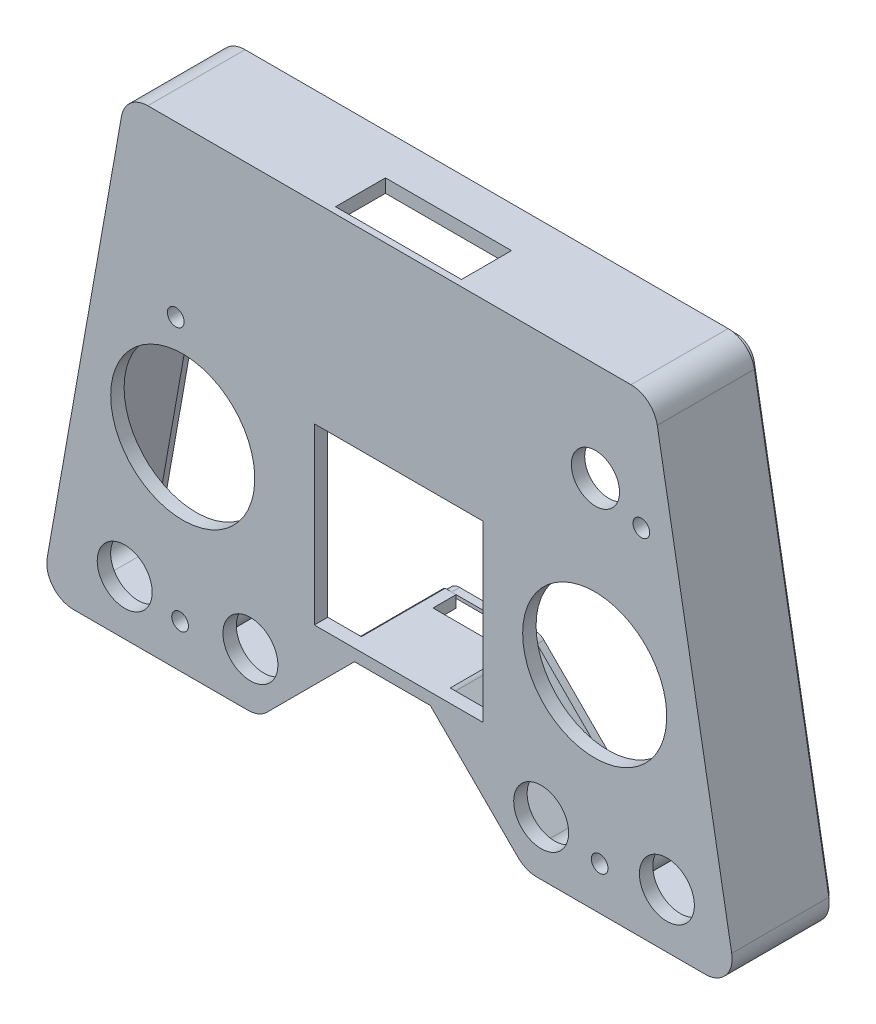
SolidWorks part; units mm, degrees
ref_plane "前视基准面" through (0, 0, 0) normal (0, 0, 1) x (1, 0, 0)
ref_plane "上视基准面" through (0, 0, 0) normal (0, 1, 0) x (1, 0, 0)
ref_plane "右视基准面" through (0, 0, 0) normal (1, 0, 0) x (0, 0, -1)
other "Configuration Table"
sketch "草图1" plane through (0, 0, 0) normal (0, 0, 1) x (1, 0, 0)
  line L0 (-11.561, 23.55) -> (-22.663, -39.125)
  line L1 (-18.737, -43.807) -> (7.32, -43.807)
  line L2 (10.139, -42.64) -> (23.192, -29.587)
  line L3 (23.201, -29.583) -> (34.512, -29.583)
  line L4 (34.521, -29.587) -> (47.574, -42.64)
  line L5 (50.393, -43.807) -> (75.552, -43.807)
  line L6 (79.479, -39.125) -> (68.376, 23.55)
  line L7 (64.45, 26.842) -> (-7.635, 26.842)
  arc A0 (-7.635, 26.842) -> (-11.561, 23.55) centre (-7.635, 22.855) ccw
  arc A1 (-22.663, -39.125) -> (-18.737, -43.807) centre (-18.737, -39.82) ccw
  arc A2 (7.32, -43.807) -> (10.139, -42.64) centre (7.3205, -39.8198) ccw
  arc A3 (23.192, -29.587) -> (23.201, -29.583) centre (23.2013, -29.5959) cw
  arc A4 (34.512, -29.583) -> (34.521, -29.587) centre (34.5117, -29.5959) cw
  arc A5 (47.574, -42.64) -> (50.393, -43.807) centre (50.3925, -39.8198) ccw
  arc A6 (75.552, -43.807) -> (79.479, -39.125) centre (75.5524, -39.8195) ccw
  arc A7 (68.376, 23.55) -> (64.45, 26.842) centre (64.45, 22.855) ccw
extrude "上壳外形_高14.5" add sketch "草图1" along normal blind 14.5
sketch "草图2" plane through (0, 0, 0) normal (0, 0, 1) x (1, 0, 0)
  line L0 (-9.591, 23.202) -> (-20.693, -39.473)
  line L1 (-18.737, -41.807) -> (7.32, -41.807)
  line L2 (8.725, -41.226) -> (21.778, -28.173)
  line L3 (23.201, -27.583) -> (34.512, -27.583)
  line L4 (35.935, -28.173) -> (48.988, -41.226)
  line L5 (50.393, -41.807) -> (75.552, -41.807)
  line L6 (77.509, -39.473) -> (66.406, 23.202)
  line L7 (64.45, 24.842) -> (-7.635, 24.842)
  arc A0 (-7.635, 24.842) -> (-9.591, 23.202) centre (-7.6347, 22.8552) ccw
  arc A1 (-20.693, -39.473) -> (-18.737, -41.807) centre (-18.7368, -39.8202) ccw
  arc A2 (7.32, -41.807) -> (8.725, -41.226) centre (7.3208, -39.8197) ccw
  arc A3 (21.778, -28.173) -> (23.201, -27.583) centre (23.2017, -29.5957) cw
  arc A4 (34.512, -27.583) -> (35.935, -28.173) centre (34.5113, -29.5957) cw
  arc A5 (48.988, -41.226) -> (50.393, -41.807) centre (50.3922, -39.8197) ccw
  arc A6 (75.552, -41.807) -> (77.509, -39.473) centre (75.5522, -39.8197) ccw
  arc A7 (66.406, 23.202) -> (64.45, 24.842) centre (64.4497, 22.8552) ccw
extrude "内部腔体_壁厚2.0" cut sketch "草图2" along normal blind 12.5
sketch "草图3" plane through (0, 0, 0) normal (0, 0, 1) x (1, 0, 0)
  circle A0 centre (-3.469, 1.614) radius 3.5
  circle A1 centre (66, 9.107) radius 3.5
  circle A2 centre (-2.822, -37.375) radius 3.5
  circle A3 centre (59.778, -37.375) radius 3.5
extrude "螺钉柱_对齐旧底壳" add sketch "草图3" along normal blind 14.5
sketch "草图4" plane through (0, 0, 0) normal (0, 0, 1) x (1, 0, 0)
  circle A0 centre (-3.469, 1.614) radius 1.25
  circle A1 centre (66, 9.107) radius 1.25
  circle A2 centre (-2.822, -37.375) radius 1.25
  circle A3 centre (59.778, -37.375) radius 1.25
extrude "M3自攻底孔_直径2.5" cut sketch "草图4" along normal through all
sketch "草图5" plane through (0, 0, 0) normal (0, 0, 1) x (1, 0, 0)
  circle A0 centre (-2.427, -13.356) radius 10.75
  circle A1 centre (59.041, -13.356) radius 10.75
  circle A2 centre (-11.089, -35.723) radius 4.1
  circle A3 centre (7.669, -35.723) radius 4.1
  circle A4 centre (51.053, -35.723) radius 4.1
  circle A5 centre (69.81, -35.723) radius 4.1
  circle A6 centre (59.147, 12.097) radius 3.6
extrude "FrontPanel_Control_Openings" cut sketch "草图5" along normal through all
sketch "草图6" plane through (0, 0, 0) normal (0, 0, 1) x (1, 0, 0)
  line L1 (17.205, -27.834) -> (42.405, -27.834)
  line L2 (17.205, -27.834) -> (17.205, -1.834)
  line L3 (17.205, -1.834) -> (42.405, -1.834)
  line L4 (42.405, -27.834) -> (42.405, -1.834)
extrude "OLED_0p96_From_Header_Toward_TypeC" cut sketch "草图6" along normal through all
sketch "草图7" plane through (0, -29.583, 0) normal (0, -1, 0) x (1, 0, 0)
  line L0 (23.86, -0.3) -> (33.41, -0.3)
  line L1 (33.41, -0.3) -> (33.41, 3.45)
  line L2 (33.41, 3.45) -> (23.86, 3.45)
  line L3 (23.86, 3.45) -> (23.86, -0.3)
extrude "USB_TypeC_Side_Opening" cut sketch "草图7" against normal blind 4
sketch "草图8" plane through (-15.2539, 2.702, 0) normal (-0.9847, 0.1744, 0) x (0, 0, 1)
  line L0 (-0.55, 14.6424) -> (-0.55, 7.9925)
  line L1 (-0.55, 7.9925) -> (3.95, 7.9925)
  line L2 (3.95, 7.9925) -> (3.95, 14.6424)
  line L3 (3.95, 14.6424) -> (-0.55, 14.6424)
extrude "SW13_Toggle_Left_Side_Opening_2026-08-11_OBJ" cut sketch "草图8" against normal blind 4
sketch "草图9" plane through (0, 26.842, 0) normal (0, 1, 0) x (1, 0, 0)
  line L0 (19.41, -6.09) -> (38.21, -6.09)
  line L1 (38.21, -6.09) -> (38.21, -13.55)
  line L2 (38.21, -13.55) -> (19.41, -13.55)
  line L3 (19.41, -13.55) -> (19.41, -6.09)
extrude "NRF24_Corrected_2026-08-11_Rear_Opening" cut sketch "草图9" against normal blind 4
sketch "草图10" plane through (0, 0, 0) normal (0, 0, 1) x (1, 0, 0)
  line L0 (-10.3298, 23.3325) -> (-21.4318, -39.3425)
  line L1 (-18.737, -42.557) -> (7.32, -42.557)
  line L2 (9.2553, -41.7563) -> (22.3083, -28.7032)
  line L3 (23.201, -28.333) -> (34.512, -28.333)
  line L4 (35.4047, -28.7032) -> (48.4578, -41.7563)
  line L5 (50.393, -42.557) -> (75.552, -42.557)
  line L6 (78.2478, -39.3425) -> (67.1448, 23.3325)
  line L7 (64.45, 25.592) -> (-7.635, 25.592)
  line L8 (-9.8373, 23.2455) -> (-20.9393, -39.4295)
  line L9 (-18.737, -42.057) -> (7.32, -42.057)
  line L10 (8.9018, -41.4027) -> (21.9547, -28.3498)
  line L11 (23.201, -27.833) -> (34.512, -27.833)
  line L12 (35.7583, -28.3498) -> (48.8113, -41.4027)
  line L13 (50.393, -42.057) -> (75.552, -42.057)
  line L14 (77.7553, -39.4295) -> (66.6523, 23.2455)
  line L15 (64.45, 25.092) -> (-7.635, 25.092)
  arc A0 (-7.635, 25.592) -> (-10.3298, 23.3325) centre (-7.6348, 22.8551) ccw
  arc A1 (-21.4318, -39.3425) -> (-18.737, -42.557) centre (-18.7369, -39.8201) ccw
  arc A2 (7.32, -42.557) -> (9.2553, -41.7563) centre (7.3207, -39.8197) ccw
  arc A3 (22.3083, -28.7032) -> (23.201, -28.333) centre (23.2016, -29.5958) cw
  arc A4 (34.512, -28.333) -> (35.4047, -28.7032) centre (34.5114, -29.5958) cw
  arc A5 (48.4578, -41.7563) -> (50.393, -42.557) centre (50.3923, -39.8197) ccw
  arc A6 (75.552, -42.557) -> (78.2478, -39.3425) centre (75.5523, -39.8196) ccw
  arc A7 (67.1448, 23.3325) -> (64.45, 25.592) centre (64.4498, 22.8551) ccw
  arc A8 (-7.635, 25.092) -> (-9.8373, 23.2455) centre (-7.6348, 22.8552) ccw
  arc A9 (-20.9393, -39.4295) -> (-18.737, -42.057) centre (-18.7368, -39.8202) ccw
  arc A10 (7.32, -42.057) -> (8.9018, -41.4027) centre (7.3208, -39.8197) ccw
  arc A11 (21.9547, -28.3498) -> (23.201, -27.833) centre (23.2016, -29.5957) cw
  arc A12 (34.512, -27.833) -> (35.7583, -28.3498) centre (34.5114, -29.5957) cw
  arc A13 (48.8113, -41.4027) -> (50.393, -42.057) centre (50.3922, -39.8197) ccw
  arc A14 (75.552, -42.057) -> (77.7553, -39.4295) centre (75.5522, -39.8197) ccw
  arc A15 (66.6523, 23.2455) -> (64.45, 25.092) centre (64.4498, 22.8552) ccw
extrude "内定位舌_避让最新PCB_0.25" add sketch "草图10" against normal blind 1.2
